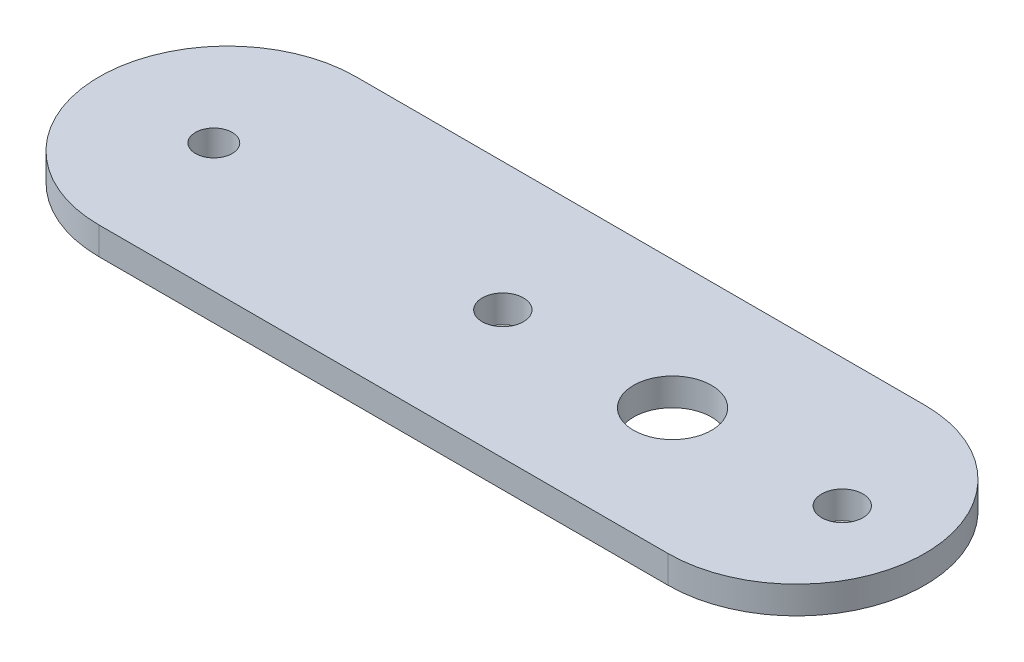
SolidWorks part; units mm, degrees
ref_plane "前视" through (0, 0, 0) normal (0, 0, 1) x (1, 0, 0)
ref_plane "上视" through (0, 0, 0) normal (0, 1, 0) x (1, 0, 0)
ref_plane "右视" through (0, 0, 0) normal (1, 0, 0) x (0, 0, -1)
sketch "草图1" plane through (0, 0, 0) normal (0, 1, 0) x (1, 0, 0)
  line L1 (-45, 14) -> (45, 14)
  line L2 (-45, 14) -> (-45, -14)
  line L3 (-45, -14) -> (45, -14)
  line L4 (45, 14) -> (45, -14)
  line L5 (-45, 14) -> (45, -14) construction
  line L6 (-45, -14) -> (45, 14) construction
  circle A0 centre (17.5, 0) radius 4.25
  circle A1 centre (-32.5, 0) radius 2
  point P0 (0, 0)
  dimension "D3" = 4
  dimension "D4" = 8.5
  dimension "D1" = 90
  dimension "D2" = 77.5
  dimension "28" = 28
  dimension "D5" = 50
extrude "凸台-拉伸1" add sketch "草图1" along normal blind 3
sketch "草图2" plane through (0, 3, 0) normal (0, 1, 0) x (1, 0, 0)
  text T0 "             <b>2</b>"
extrude "凸台-拉伸2" [suppressed] add sketch "草图2" along normal blind 0.5
sketch "草图3" plane through (0, 3, 0) normal (0, 1, 0) x (1, 0, 0)
  circle A0 centre (36, 0) radius 2.25
  circle A1 centre (-1, 0) radius 2.25
  point P4 (17.5, 0)
  dimension "D3" = 4.5
  dimension "D4" = 4.5
  dimension "D1" = 37
  dimension "D2" = 18.5
extrude "切除-拉伸1" cut sketch "草图3" against normal up to next
fillet "圆角1" 2 edges at (-45, 1.5, 14) (-45, 1.5, -14) type full round first side face at (0, 1.5, 14) second side face at (0, 1.5, -14) middle face at (-45, 1.5, 0)
fillet "圆角2" 2 edges at (45, 1.5, -14) (45, 1.5, 14) type full round first side face at (7, 1.5, -14) second side face at (7, 1.5, 14) middle face at (45, 1.5, 0)
